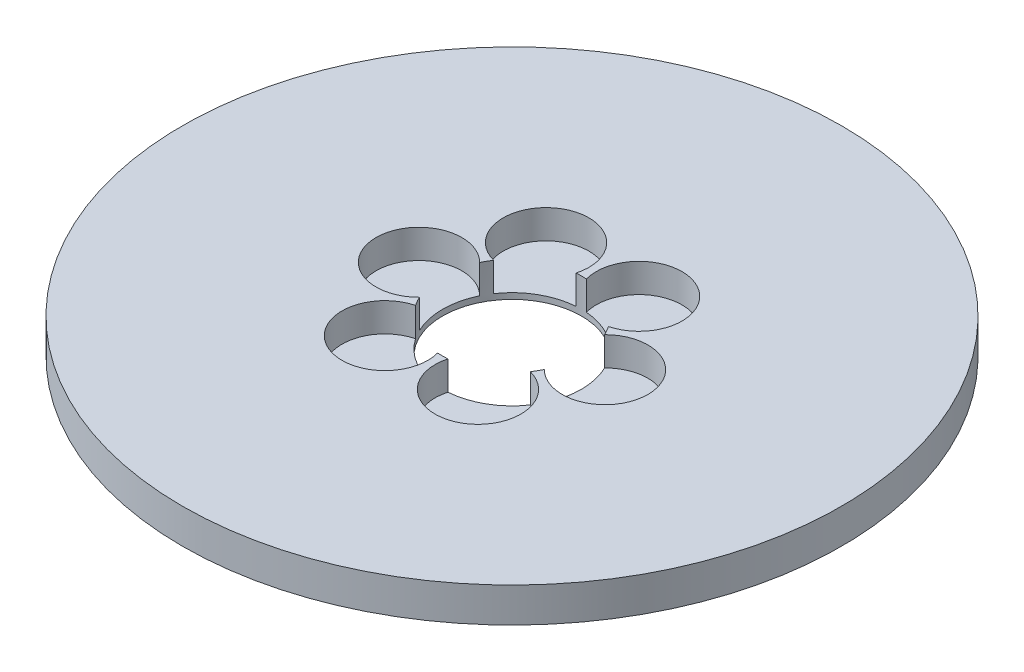
SolidWorks part; units mm, degrees
ref_plane "Front Plane" through (0, 0, 0) normal (0, 0, 1) x (1, 0, 0)
ref_plane "Top Plane" through (0, 0, 0) normal (0, 1, 0) x (1, 0, 0)
ref_plane "Right Plane" through (0, 0, 0) normal (1, 0, 0) x (0, 0, -1)
sketch "Sketch1" plane through (0, 0, 0) normal (0, 1, 0) x (1, 0, 0)
  circle A0 centre (0, 0) radius 47.5
  dimension "FLANGE_OD" = 95
extrude "Boss-Extrude1" add sketch "Sketch1" along normal blind 5
sketch "Sketch2" plane through (0, 0, 0) normal (0, 1, 0) x (1, 0, 0)
  circle A0 centre (0, 0) radius 10
  dimension "BORE_D" = 20
extrude "Cut-Extrude1" cut sketch "Sketch2" along normal through all
sketch "Sketch3" plane through (0, 5, 0) normal (0, 1, 0) x (1, 0, 0)
  circle A0 centre (0, 0) radius 13.4101 construction
  circle A1 centre (-13.4101, 0) radius 6.1833
  dimension "BOLT_D" = 12.3666
  dimension "BOLT_PCD" = 26.8203
extrude "Cut-Extrude2" cut sketch "Sketch3" against normal blind 4.1559
pattern_circular "CirPattern1" count 6 over 360 about axis through (0, 0, 0) along (0, 1, 0) of "Cut-Extrude2"
